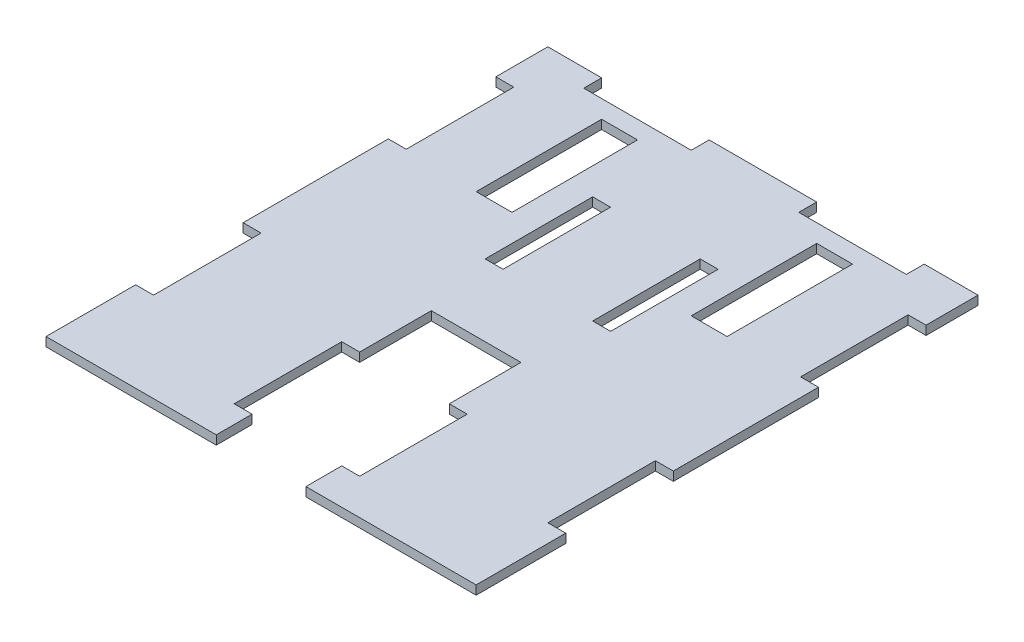
SolidWorks part; units mm, degrees
ref_plane "Front Plane" through (0, 0, 0) normal (0, 0, 1) x (1, 0, 0)
ref_plane "Top Plane" through (0, 0, 0) normal (0, 1, 0) x (1, 0, 0)
ref_plane "Right Plane" through (0, 0, 0) normal (1, 0, 0) x (0, 0, -1)
sketch "Sketch1" plane through (0, 0, 0) normal (0, 1, 0) x (1, 0, 0)
  line L1 (-152.4, -177.8) -> (152.4, -177.8)
  line L2 (-152.4, -177.8) -> (-152.4, 177.8)
  line L3 (-152.4, 177.8) -> (152.4, 177.8)
  line L4 (152.4, -177.8) -> (152.4, 177.8)
  line L5 (-152.4, -177.8) -> (152.4, 177.8) construction
  line L6 (-152.4, 177.8) -> (152.4, -177.8) construction
  point P0 (0, 0)
  dimension "D1" = 355.6
  dimension "D2" = 304.8
extrude "Boss-Extrude1" add sketch "Sketch1" along normal blind 6.35
sketch "Sketch2" plane through (0, 6.35, 0) normal (0, 1, 0) x (1, 0, 0)
  line L0 (-152.4, -177.8) -> (152.4, -177.8) construction
  line L1 (-31.75, -25.4) -> (31.75, -25.4)
  line L2 (-31.75, -25.4) -> (-31.75, -177.8)
  line L3 (-31.75, -177.8) -> (31.75, -177.8)
  line L4 (31.75, -25.4) -> (31.75, -177.8)
  line L5 (-31.75, -25.4) -> (31.75, -177.8) construction
  line L6 (-31.75, -177.8) -> (31.75, -25.4) construction
  point P0 (0, -101.6)
  dimension "D1" = 152.4
  dimension "D2" = 63.5
extrude "Cut-Extrude1" cut sketch "Sketch2" against normal through all
sketch "Sketch3" plane through (0, 6.35, 0) normal (0, 1, 0) x (1, 0, 0)
  line L0 (152.4, -177.8) -> (152.4, 177.8) construction
  line L1 (88.9, 152.4) -> (63.5, 152.4)
  line L2 (88.9, 152.4) -> (88.9, 63.5)
  line L3 (88.9, 63.5) -> (63.5, 63.5)
  line L4 (63.5, 152.4) -> (63.5, 63.5)
  line L5 (152.4, 177.8) -> (-152.4, 177.8) construction
  line L6 (0, -3.4925) -> (0, 3.4925) construction
  line L7 (-88.9, 63.5) -> (-63.5, 63.5)
  line L8 (-63.5, 152.4) -> (-63.5, 63.5)
  line L9 (-88.9, 152.4) -> (-63.5, 152.4)
  line L10 (-88.9, 152.4) -> (-88.9, 63.5)
  dimension "D1" = 63.5
  dimension "D2" = 88.9
  dimension "D3" = 25.4
  dimension "D4" = 114.3
extrude "Cut-Extrude2" cut sketch "Sketch3" against normal through all
sketch "Sketch4" plane through (0, 6.35, 0) normal (0, 1, 0) x (1, 0, 0)
  line L0 (-152.4, 177.8) -> (-152.4, -177.8) construction
  line L1 (-152.4, 140.97) -> (-139.7, 140.97)
  line L2 (-152.4, 140.97) -> (-152.4, 64.77)
  line L3 (-152.4, 64.77) -> (-139.7, 64.77)
  line L4 (-139.7, 140.97) -> (-139.7, 64.77)
  line L5 (0, -3.4925) -> (0, 3.4925) construction
  line L6 (-152.4, -114.3) -> (-139.7, -114.3)
  line L7 (-152.4, -114.3) -> (-152.4, -38.1)
  line L8 (-152.4, -38.1) -> (-139.7, -38.1)
  line L9 (-139.7, -114.3) -> (-139.7, -38.1)
  line L10 (152.4, 64.77) -> (139.7, 64.77)
  line L11 (139.7, 140.97) -> (139.7, 64.77)
  line L12 (152.4, 140.97) -> (139.7, 140.97)
  line L13 (152.4, 140.97) -> (152.4, 64.77)
  line L14 (152.4, -38.1) -> (139.7, -38.1)
  line L15 (139.7, -114.3) -> (139.7, -38.1)
  line L16 (152.4, -114.3) -> (139.7, -114.3)
  line L17 (152.4, -114.3) -> (152.4, -38.1)
  line L18 (152.4, 177.8) -> (-152.4, 177.8) construction
  line L19 (114.3, 165.1) -> (38.1, 165.1)
  line L20 (-114.3, 177.8) -> (-38.1, 177.8)
  line L21 (-114.3, 177.8) -> (-114.3, 165.1)
  line L22 (-114.3, 165.1) -> (-38.1, 165.1)
  line L23 (-38.1, 177.8) -> (-38.1, 165.1)
  line L24 (38.1, 177.8) -> (38.1, 165.1)
  line L25 (114.3, 177.8) -> (38.1, 177.8)
  line L26 (114.3, 177.8) -> (114.3, 165.1)
  line L27 (-31.75, -25.4) -> (-31.75, -177.8) construction
  line L28 (-31.75, -152.4) -> (-44.45, -152.4)
  line L29 (-31.75, -152.4) -> (-31.75, -76.2)
  line L30 (-31.75, -76.2) -> (-44.45, -76.2)
  line L31 (-44.45, -152.4) -> (-44.45, -76.2)
  line L32 (-152.4, -177.8) -> (-31.75, -177.8) construction
  line L33 (31.75, 101.6) -> (44.45, 101.6)
  line L34 (-31.75, 25.4) -> (-44.45, 25.4)
  line L35 (-31.75, 25.4) -> (-31.75, 101.6)
  line L36 (-31.75, 101.6) -> (-44.45, 101.6)
  line L37 (-44.45, 25.4) -> (-44.45, 101.6)
  line L38 (44.45, 25.4) -> (44.45, 101.6)
  line L39 (31.75, 25.4) -> (44.45, 25.4)
  line L40 (31.75, 25.4) -> (31.75, 101.6)
  line L41 (31.75, -76.2) -> (44.45, -76.2)
  line L42 (44.45, -152.4) -> (44.45, -76.2)
  line L43 (31.75, -152.4) -> (44.45, -152.4)
  line L44 (31.75, -152.4) -> (31.75, -76.2)
  dimension "D1" = 12.7
  dimension "D2" = 12.7
  dimension "D3" = 76.2
  dimension "D4" = 76.2
  dimension "D5" = 36.83
  dimension "D6" = 215.9
  dimension "D7" = 12.7
  dimension "D8" = 76.2
  dimension "D9" = 76.2
  dimension "D10" = 12.7
  dimension "D11" = 76.2
  dimension "D12" = 25.4
  dimension "D13" = 76.2
  dimension "D14" = 12.7
  dimension "D15" = 203.2
extrude "Cut-Extrude3" cut sketch "Sketch4" against normal through all
